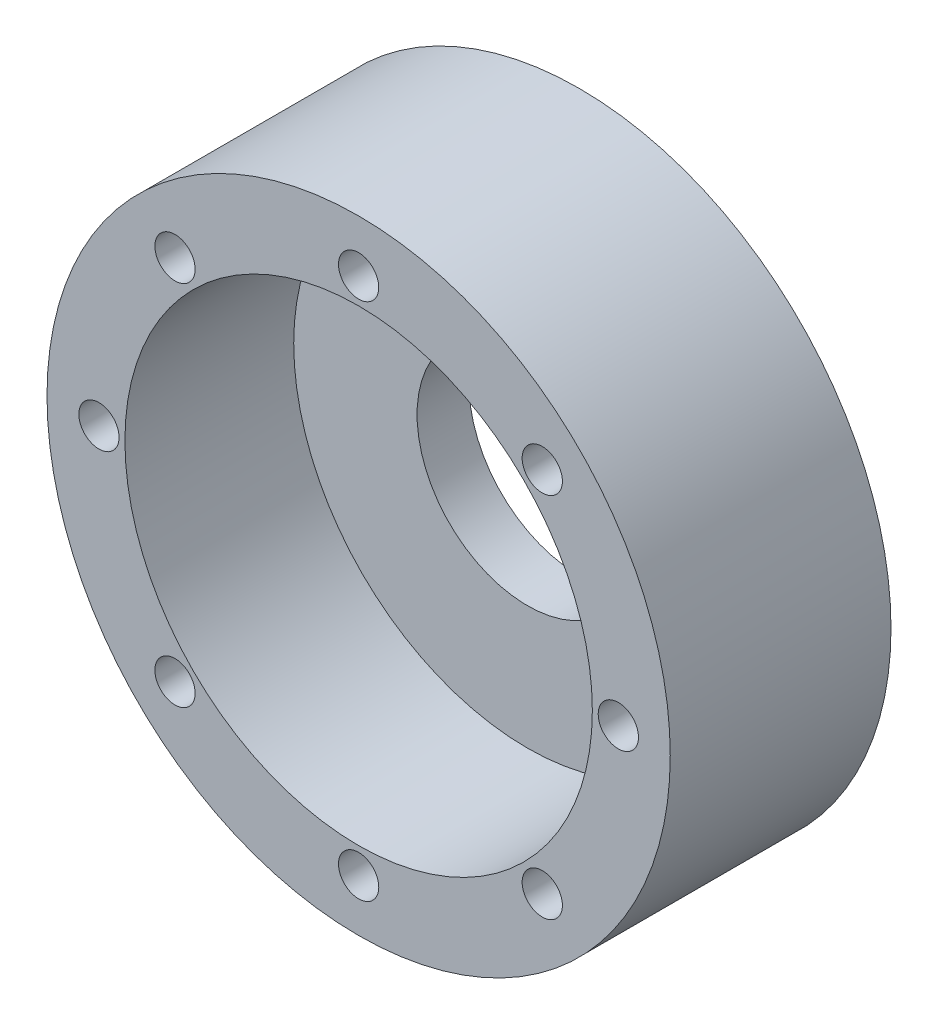
SolidWorks part; units mm, degrees
ref_plane "Front Plane" through (0, 0, 0) normal (0, 0, 1) x (1, 0, 0)
ref_plane "Top Plane" through (0, 0, 0) normal (0, 1, 0) x (1, 0, 0)
ref_plane "Right Plane" through (0, 0, 0) normal (1, 0, 0) x (0, 0, -1)
ref_axis "Axis1" through (0, 0, 5.5) along (0, 0, -1)
sketch "Sketch6" plane through (0, 0, 0) normal (0, 0, 1) x (1, 0, 0)
  line L0 (0, 0) -> (0, 20) construction
  circle A0 centre (0, 0) radius 24
  circle A1 centre (0, 20) radius 1.55
  circle A2 centre (14.1421, 14.1421) radius 1.55
  circle A3 centre (20, 0) radius 1.55
  circle A4 centre (14.1421, -14.1421) radius 1.55
  circle A5 centre (0, -20) radius 1.55
  circle A6 centre (-14.1421, -14.1421) radius 1.55
  circle A7 centre (-20, 0) radius 1.55
  circle A8 centre (-14.1421, 14.1421) radius 1.55
  circle A9 centre (0, 0) radius 8.5
  point P21 (0, 0)
  dimension "D1" = 8
extrude "Boss-Extrude1" add sketch "Sketch6" along normal blind 17
sketch "Sketch8" plane through (0, 0, 0) normal (0, 0, -1) x (-1, 0, 0)
  line L0 (0, 20) -> (0, 0) construction
  circle A0 centre (0, 20) radius 3.5
  circle A1 centre (14.1421, 14.1421) radius 3.5
  circle A2 centre (20, 0) radius 3.5
  circle A3 centre (14.1421, -14.1421) radius 3.5
  circle A4 centre (0, -20) radius 3.5
  circle A5 centre (-14.1421, -14.1421) radius 3.5
  circle A6 centre (-20, 0) radius 3.5
  circle A7 centre (-14.1421, 14.1421) radius 3.5
  point P20 (0, 0)
  dimension "D1" = 8
extrude "Cut-Extrude6" cut sketch "Sketch8" against normal blind 3
sketch "Sketch9" plane through (0, 0, 17) normal (0, 0, 1) x (1, 0, 0)
  circle A0 centre (0, 0) radius 18
extrude "Cut-Extrude7" cut sketch "Sketch9" against normal blind 13
